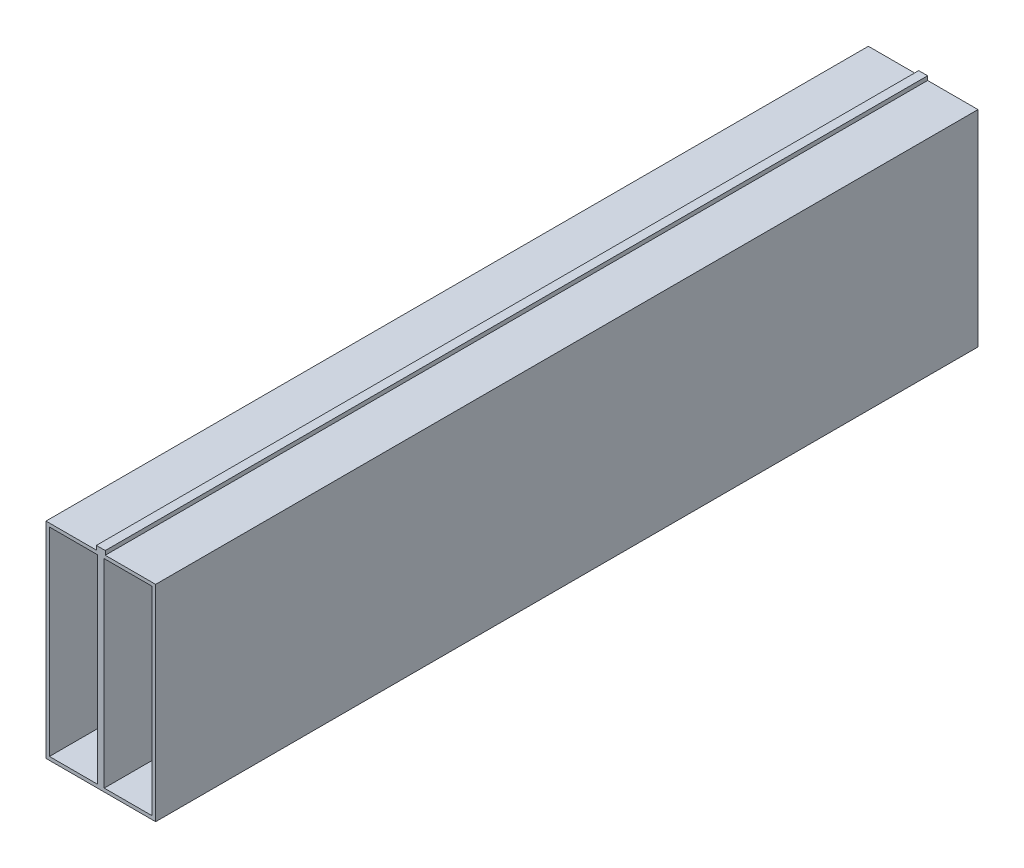
SolidWorks part; units mm, degrees
ref_plane "Plan de face" through (0, 0, 0) normal (0, 0, 1) x (1, 0, 0)
ref_plane "Plan de dessus" through (0, 0, 0) normal (0, 1, 0) x (1, 0, 0)
ref_plane "Plan de droite" through (0, 0, 0) normal (1, 0, 0) x (0, 0, -1)
sketch "Esquisse1" plane through (0, 0, 0) normal (0, 0, 1) x (1, 0, 0)
  line L0 (425, 1475) -> (425, 25)
  line L1 (0, 0) -> (800, 0)
  line L2 (0, 0) -> (0, 1500)
  line L3 (0, 1500) -> (800, 1500)
  line L4 (800, 0) -> (800, 1500)
  line L5 (25, 1475) -> (375, 1475)
  line L6 (25, 1475) -> (25, 25)
  line L7 (25, 25) -> (375, 25)
  line L8 (375, 1475) -> (375, 25)
  line L9 (425, 25) -> (775, 25)
  line L10 (775, 25) -> (775, 1475)
  line L11 (775, 1475) -> (425, 1475)
  line L12 (400, -1) -> (400, 1) construction
  point P16 (400, 0)
  dimension "D1" = 1500
  dimension "D2" = 800
  dimension "D3" = 25
  dimension "D4" = 25
  dimension "D5" = 25
  dimension "D6" = 25
  dimension "D7" = 25
  dimension "D8" = 25
  dimension "D9" = 25
  dimension "D10" = 25
extrude "Boss.-Extru.1" add sketch "Esquisse1" against normal blind 6000
sketch "Esquisse2" plane through (0, 0, 0) normal (0, 0, 1) x (1, 0, 0)
  line L0 (400, 1500) -> (400, 1546.5728) construction
  line L1 (800, 1500) -> (0, 1500) construction
  line L2 (367.5, 1500) -> (432.5, 1500)
  line L3 (432.5, 1500) -> (432.5, 1530)
  line L4 (432.5, 1530) -> (367.5, 1530)
  line L5 (367.5, 1530) -> (367.5, 1500)
  point P7 (400, 1500)
  dimension "D1" = 65
  dimension "D2" = 30
extrude "Boss.-Extru.2" add sketch "Esquisse2" against normal up to surface (6000 mm away) up to face at (600, 750, -6000)
